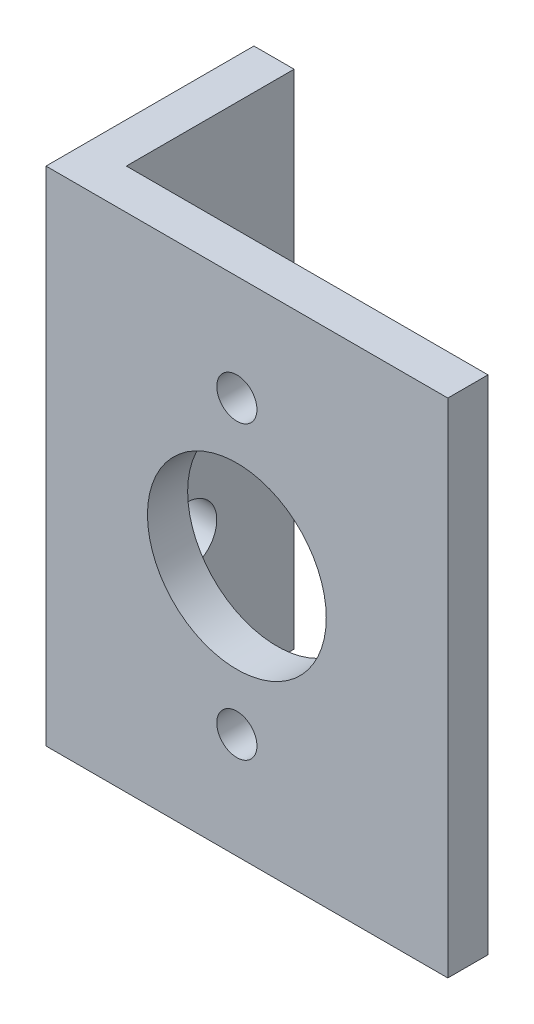
SolidWorks part; units mm, degrees
ref_plane "Спереди" through (0, 0, 0) normal (0, 0, 1) x (1, 0, 0)
ref_plane "Сверху" through (0, 0, 0) normal (0, 1, 0) x (1, 0, 0)
ref_plane "Справа" through (0, 0, 0) normal (1, 0, 0) x (0, 0, -1)
sketch "Эскиз1" plane through (0, 0, 0) normal (0, 1, 0) x (1, 0, 0)
  line L1 (0, 0) -> (40, 0)
  line L2 (0, 0) -> (0, 4)
  line L3 (4, 4) -> (40, 4)
  line L4 (40, 0) -> (40, 4)
  line L6 (0, 4) -> (0, 20.7)
  line L7 (0, 20.7) -> (4, 20.7)
  line L8 (4, 4) -> (4, 20.7)
  dimension "D1" = 40
  dimension "D2" = 4
  dimension "D3" = 20.7
  dimension "D4" = 4
extrude "Бобышка-Вытянуть1" add sketch "Эскиз1" along normal blind 50
sketch "Эскиз2" plane through (0, 0, 0) normal (-1, 0, 0) x (0, 0, 1)
  line L0 (-10, 50) -> (-10, 0) construction
  line L1 (-20.7, 50) -> (0, 50) construction
  line L3 (0, 50) -> (0, 0) construction
  circle A0 centre (-10, 35) radius 3
  circle A1 centre (-10, 15) radius 3
  dimension "D2" = 6
  dimension "D3" = 6
  dimension "D1" = 10
  dimension "D4" = 15
  dimension "D5" = 20
extrude "Вырез-Вытянуть1" cut sketch "Эскиз2" against normal blind 4
sketch "Эскиз3" plane through (0, 0, -4) normal (0, 0, -1) x (-1, 0, 0)
  line L0 (-19, 50) -> (-19, 0) construction
  line L1 (-40, 50) -> (-4, 50) construction
  line L2 (-4, 50) -> (-4, 0) construction
  circle A0 centre (-19, 25) radius 8.9
  circle A1 centre (-19, 39.5) radius 2
  circle A2 centre (-19, 10.5) radius 2
  dimension "D2" = 17.8
  dimension "D4" = 4
  dimension "D5" = 4
  dimension "D1" = 15
  dimension "D3" = 25
  dimension "D6" = 29
  dimension "D7" = 14.5
extrude "Вырез-Вытянуть2" cut sketch "Эскиз3" against normal blind 4
